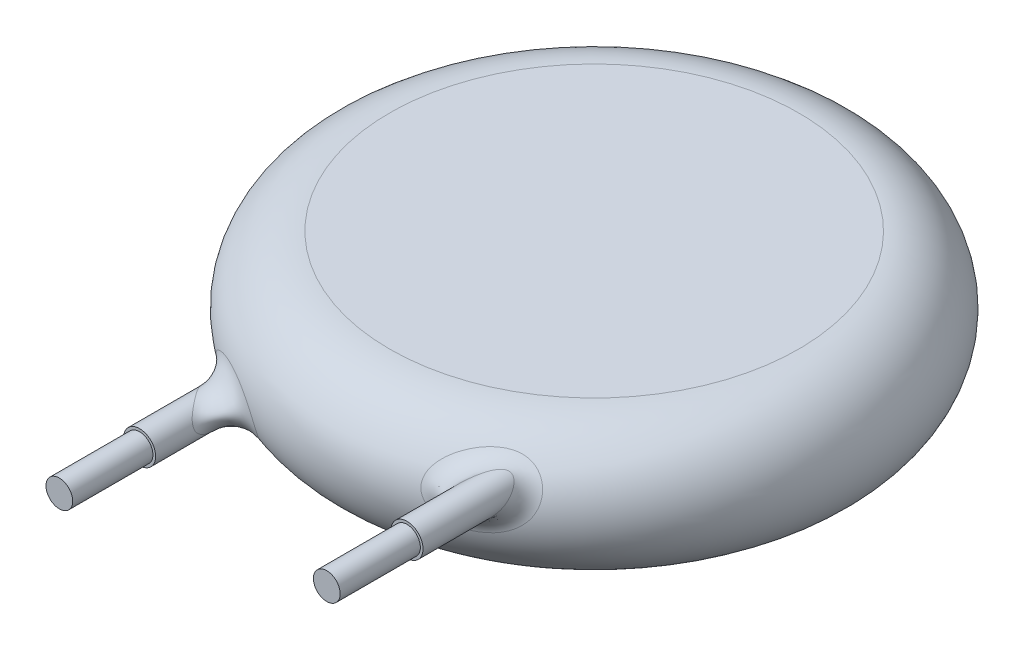
SolidWorks part; units mm, degrees
ref_plane "Front Plane" through (0, 0, 0) normal (0, 0, 1) x (1, 0, 0)
ref_plane "Top Plane" through (0, 0, 0) normal (0, 1, 0) x (1, 0, 0)
ref_plane "Right Plane" through (0, 0, 0) normal (1, 0, 0) x (0, 0, -1)
sketch "Sketch1" plane through (0, 0, 0) normal (0, 0, 1) x (1, 0, 0)
  line L0 (0, 12.9726) -> (0, -9.7806) construction
  line L1 (7.65, 2.5) -> (0, 2.5)
  line L2 (0, 2.5) -> (0, -2.5)
  line L3 (0, -2.5) -> (7.65, -2.5)
  arc A0 (7.65, -2.5) -> (7.65, 2.5) centre (7.65, 0) ccw
  dimension "D1" = 5
  dimension "D2" = 20.3
  dimension "D3" = 2.5
revolve "Revolve1" add sketch "Sketch1" angle 360 about L0
ref_plane "Plane1" through (0, 0, -11.5) normal (0, 0, 1) x (1, 0, 0)
ref_plane "Plane2" through (0, 0, 12) normal (0, 0, 1) x (1, 0, 0)
sketch "Sketch3" plane through (0, 0, 12) normal (0, 0, 1) x (1, 0, 0)
  line L0 (-8.004, 0) -> (8.0735, 0) construction
  line L1 (0, 6.2434) -> (0, -6.2434) construction
  circle A0 centre (5, 1) radius 0.6
  circle A1 centre (-5, -1) radius 0.6
  dimension "D1" = 1.2
  dimension "D2" = 5
  dimension "D3" = 10
  dimension "D4" = 1
  dimension "D5" = 2
extrude "Extrude1" add sketch "Sketch3" against normal up to next
fillet "Fillet1" radius 1 2 edges at (-4.6482, -0.5139, 8.963) (4.4063, 1.0864, 8.8672)
sketch "Sketch4" plane through (0, 0, 12) normal (0, 0, 1) x (1, 0, 0)
  circle A0 centre (5, 1) radius 0.5
  circle A1 centre (-5, -1) radius 0.5
  dimension "D1" = 1
extrude "Extrude2" add sketch "Sketch4" along normal blind 3
